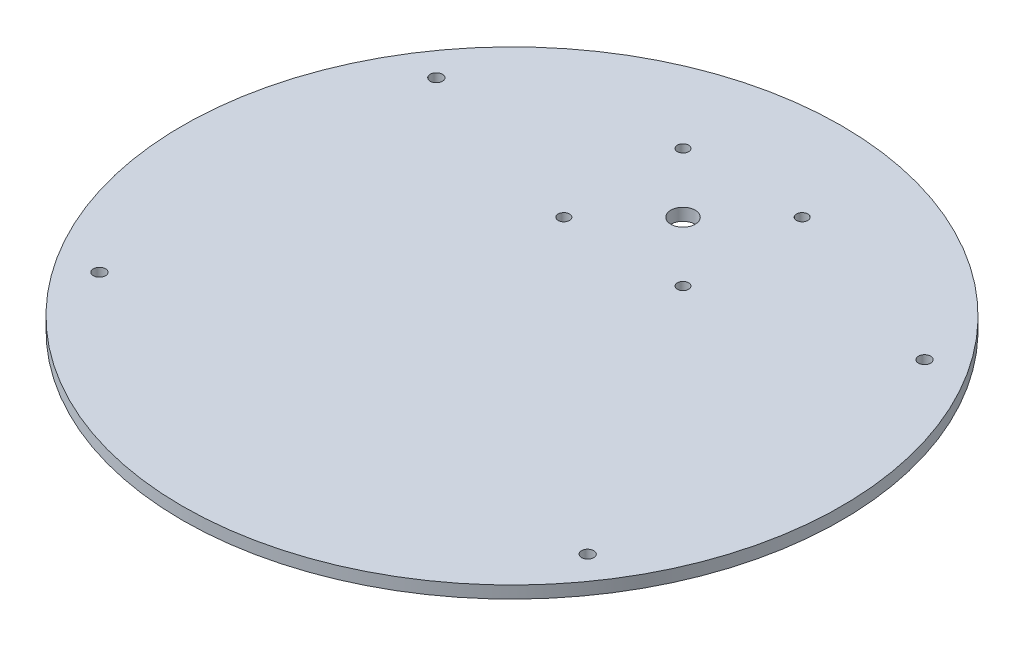
SolidWorks part; units mm, degrees
ref_plane "Front Plane" through (0, 0, 0) normal (0, 0, 1) x (1, 0, 0)
ref_plane "Top Plane" through (0, 0, 0) normal (0, 1, 0) x (1, 0, 0)
ref_plane "Right Plane" through (0, 0, 0) normal (1, 0, 0) x (0, 0, -1)
sketch "Sketch1" plane through (0, 0, 0) normal (0, 1, 0) x (1, 0, 0)
  circle A0 centre (0, 0) radius 85.725
  dimension "D1" = 171.45
extrude "Boss-Extrude1" add sketch "Sketch1" along normal blind 3.175
sketch "Sketch2" plane through (0, 3.175, 0) normal (0, 1, 0) x (1, 0, 0)
  line L0 (-63.5, 43.815) -> (-63.5, -43.815) construction
  line L1 (-63.5, -43.815) -> (63.5, -43.815) construction
  line L2 (63.5, -43.815) -> (63.5, 43.815) construction
  line L3 (63.5, 43.815) -> (-63.5, 43.815) construction
  circle A0 centre (-63.5, 43.815) radius 1.5875
  circle A1 centre (63.5, 43.815) radius 1.5875
  circle A2 centre (-63.5, -43.815) radius 1.5875
  circle A3 centre (63.5, -43.815) radius 1.5875
  dimension "D1" = 3.175
  dimension "D2" = 3.175
  dimension "D3" = 127
  dimension "D4" = 3.175
  dimension "D5" = 3.175
  dimension "D6" = 87.63
  dimension "D7" = 87.63
  dimension "D8" = 43.815
  dimension "D9" = 63.5
extrude "Cut-Extrude1" cut sketch "Sketch2" against normal up to next
sketch "Sketch3" plane through (0, 3.175, 0) normal (0, 1, 0) x (1, 0, 0)
  line L0 (0, 44.4822) -> (0, 0) construction
  circle A0 centre (0, 44.4822) radius 3.175
  dimension "D1" = 6.35
  dimension "D2" = 44.4822
extrude "Cut-Extrude2" cut sketch "Sketch3" against normal up to next contours A0
ref_axis "Axis1" through (0, 3.175, 0) along (0, -1, 0)
sketch "Sketch5" plane through (0, 3.175, 0) normal (0, 1, 0) x (1, 0, 0)
  line L1 (-15.5004, 59.9825) -> (15.5003, 59.9825) construction
  line L2 (-15.5004, 59.9825) -> (-15.5003, 28.9818) construction
  line L3 (-15.5003, 28.9818) -> (15.5003, 28.9818) construction
  line L4 (15.5003, 59.9825) -> (15.5003, 28.9818) construction
  line L5 (-15.5004, 59.9825) -> (15.5003, 28.9818) construction
  line L6 (-15.5003, 28.9818) -> (15.5003, 59.9825) construction
  circle A0 centre (0, 44.4822) radius 3.175 construction
  circle A1 centre (0, 44.4822) radius 3.175 construction
  circle A2 centre (-15.5004, 59.9825) radius 1.4732
  circle A3 centre (15.5003, 59.9825) radius 1.4732
  circle A4 centre (-15.5003, 28.9818) radius 1.4732
  circle A5 centre (15.5003, 28.9818) radius 1.4732
  dimension "D3" = 2.9464
  dimension "D4" = 2.9464
  dimension "D5" = 2.9464
  dimension "D6" = 2.9464
  dimension "D1" = 31.0007
  dimension "D2" = 31.0007
extrude "Cut-Extrude3" cut sketch "Sketch5" against normal up to next
